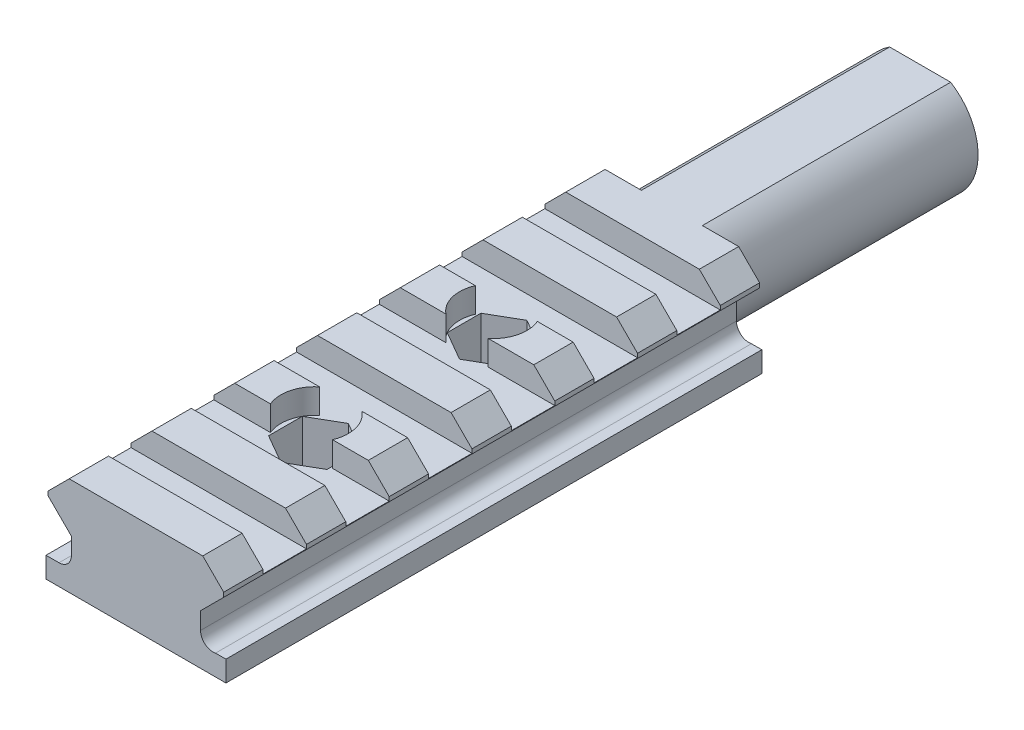
SolidWorks part; units mm, degrees
ref_plane "Front Plane" through (0, 0, 0) normal (0, 0, 1) x (1, 0, 0)
ref_plane "Top Plane" through (0, 0, 0) normal (0, 1, 0) x (1, 0, 0)
ref_plane "Right Plane" through (0, 0, 0) normal (1, 0, 0) x (0, 0, -1)
sketch "Sketch2" plane through (0, 0, 0) normal (0, 0, 1) x (1, 0, 0)
  line L0 (-9.5, -1.37) -> (9.5, -1.37)
  line L1 (-9.5, -1.37) -> (-9.5, 1.37)
  line L2 (9.5, -1.37) -> (9.5, 1.37)
  line L3 (-9.5, 1.37) -> (9.5, 1.37)
  line L4 (-9.5, -1.37) -> (9.5, 1.37) construction
  line L5 (9.5, -1.37) -> (-9.5, 1.37) construction
  line L6 (0, 0) -> (10.6, 0)
  line L7 (0, 0) -> (-10.6, 0)
  line L8 (0, 0) -> (0, -6.6)
  line L9 (0, -6.6) -> (7.8, -6.6)
  line L10 (0, -6.6) -> (-7.8, -6.6)
  line L11 (0, -1.37) -> (0, 2.8)
  line L12 (0, 2.8) -> (-18.1258, 2.8) construction
  line L13 (0, 2.8) -> (21.089, 2.8) construction
  line L14 (-8.07, 2.8) -> (8.07, 2.8)
  line L15 (-8.07, 2.8) -> (-10.87, 0)
  line L16 (-10.87, 0) -> (-7.8, -3.07)
  line L17 (-7.8, -3.07) -> (-7.8, -5.1)
  line L18 (8.07, 2.8) -> (10.87, 0)
  line L19 (7.8, -3.07) -> (10.87, 0)
  line L20 (-9.3, -6.6) -> (-10.87, -6.6)
  line L21 (7.8, -3.07) -> (7.8, -5.1331)
  line L22 (9.6133, -6.6) -> (10.87, -6.6)
  line L23 (10.87, -6.6) -> (10.87, -9.1)
  line L24 (10.87, -9.1) -> (-10.87, -9.1)
  line L25 (-10.87, -9.1) -> (-10.87, -6.6)
  line L26 (-10.6, 0) -> (-10.6, 0.27)
  line L27 (-10.6, 0) -> (-10.6, -0.27)
  line L28 (10.6, 0) -> (10.6, 0.27)
  line L29 (10.6, 0) -> (10.6, -0.27)
  arc A0 (-7.8, -5.1) -> (-9.3, -6.6) centre (-9.3, -5.1) cw
  arc A1 (7.8, -5.1331) -> (9.6133, -6.6) centre (9.3, -5.1331) ccw
  point P1 (0, 0)
  point P28 (0, 0)
  dimension "D8" = 1.5
  dimension "D9" = 1.5
  dimension "D1" = 2.74
  dimension "D2" = 19
  dimension "D3" = 10.6
  dimension "D4" = 10.6
  dimension "D5" = 15.6
  dimension "D6" = 4.17
  dimension "D7" = 9.4
  dimension "D10" = 2.5
  dimension "D11" = 21.74
  dimension "D12" = 9.6133
extrude "Boss-Extrude1" add sketch "Sketch2" along normal blind 64.75 contours A1 L21 L19 L0 L16 L17 A0 L20 L25 L24 L23 L22 | L7 L11 L3 L1 | L8 L7 L1 L0 | L6 L8 L0 L2 | L11 L6 L2 L3 | L6 L28 L18 L2 | L29 L6 L2 L19 | L7 L27 L16 L1 | L26 L7 L1 L15 | L14 L15 L3 L11 | L18 L14 L11 L3 region at (-4.75, -0.685, 0) region at (-9.927, -0.4715, 0) region at (-0.0035, -5.4607, 0) region at (4.75, -0.685, 0) region at (-9.927, 0.4715, 0) region at (-4.75, 0.685, 0) region at (9.927, -0.4715, 0) region at (4.75, 0.685, 0) region at (-4.4022, 2.0656, 0) region at (9.927, 0.4715, 0) region at (4.4022, 2.0656, 0)
sketch "Sketch3" plane through (-10.87, 0, 0) normal (-1, 0, 0) x (0, 0, 1)
  line L0 (0, -9.1) -> (0, 2.8)
  line L1 (0, 2.8) -> (4.75, 2.8)
  line L2 (64.75, 2.8) -> (0, 2.8) construction
  line L3 (14.75, 2.8) -> (14.75, -0.2)
  line L4 (4.75, 2.8) -> (10, 2.8)
  line L5 (4.75, 2.8) -> (4.75, -0.2)
  line L6 (4.75, -0.2) -> (10, -0.2)
  line L7 (10, 2.8) -> (10, -0.2)
  line L8 (14.75, 2.8) -> (20, 2.8)
  line L9 (20, 2.8) -> (20, -0.2)
  line L10 (14.75, -0.2) -> (20, -0.2)
  line L11 (24.75, 2.8) -> (24.75, -0.2)
  line L12 (24.75, 2.8) -> (30, 2.8)
  line L13 (30, 2.8) -> (30, -0.2)
  line L14 (24.75, -0.2) -> (30, -0.2)
  line L15 (34.75, 2.8) -> (34.75, -0.2)
  line L16 (34.75, 2.8) -> (40, 2.8)
  line L17 (40, 2.8) -> (40, -0.2)
  line L18 (34.75, -0.2) -> (40, -0.2)
  line L19 (44.75, 2.8) -> (44.75, -0.2)
  line L20 (44.75, 2.8) -> (50, 2.8)
  line L21 (50, 2.8) -> (50, -0.2)
  line L22 (44.75, -0.2) -> (50, -0.2)
  line L23 (54.75, 2.8) -> (54.75, -0.2)
  line L24 (54.75, 2.8) -> (60, 2.8)
  line L25 (60, 2.8) -> (60, -0.2)
  line L26 (54.75, -0.2) -> (60, -0.2)
  line L27 (0, -9.1) -> (0, -6.6) construction
  dimension "D1" = 4.75
  dimension "D2" = 3
  dimension "D3" = 5.25
  dimension "D4" = 6
  dimension "D5" = 14.75
extrude "Cut-Extrude1" cut sketch "Sketch3" against normal blind 60 contours L7 L4 L5 L6 | L3 L10 L9 L8 | L11 L14 L13 L12 | L15 L18 L17 L16 | L19 L22 L21 L20 | L23 L26 L25 L24 region at (-10.87, 1.3, 17.375) region at (-10.87, 1.3, 7.375) region at (-10.87, 1.3, 27.375) region at (-10.87, 1.3, 37.375) region at (-10.87, 1.3, 47.375) region at (-10.87, 1.3, 57.375)
sketch "Sketch4" plane through (0, 2.8, 0) normal (0, 1, 0) x (1, 0, 0)
  line L0 (0, 0) -> (0, -21.5833)
  line L1 (0, -64.75) -> (0, -43.1667)
  line L2 (0, -17.513) -> (-3.525, -19.5482)
  line L3 (-3.525, -19.5482) -> (-3.525, -23.6185)
  line L4 (-3.525, -23.6185) -> (0, -25.6537)
  line L5 (0, -25.6537) -> (3.525, -23.6185)
  line L6 (3.525, -23.6185) -> (3.525, -19.5482)
  line L7 (3.525, -19.5482) -> (0, -17.513)
  line L8 (-8.07, -64.75) -> (8.07, -64.75) construction
  line L10 (0, -47.237) -> (3.525, -45.2018)
  line L11 (3.525, -45.2018) -> (3.525, -41.1315)
  line L12 (3.525, -41.1315) -> (0, -39.0963)
  line L13 (0, -39.0963) -> (-3.525, -41.1315)
  line L14 (-3.525, -41.1315) -> (-3.525, -45.2018)
  line L15 (-3.525, -45.2018) -> (0, -47.237)
  circle A0 centre (0, -21.5833) radius 3.525 construction
  circle A1 centre (0, -43.1667) radius 3.525 construction
  circle A2 centre (0, -21.5833) radius 2.025
  circle A3 centre (0, -43.1667) radius 2.025
  circle A4 centre (0, -21.5833) radius 4.0703
  circle A5 centre (0, -43.1667) radius 4.0703
  dimension "D1" = 21.5833
  dimension "D2" = 7.05
  dimension "D3" = 7.05
extrude "Cut-Extrude2" cut sketch "Sketch4" against normal blind 9.1 contours A2 L2 L3 L4 L5 L6 L7 | A3 L10 L11 L12 L13 L14 L15 region at (1.7087, 2.8, 18.6239) region at (-1.7087, 2.8, 46.1261)
extrude "Cut-Extrude3" cut sketch "Sketch4<4>" against normal blind 59.1 contours A2 | A3 region at (1.3914, 2.8, 20.1919) region at (-1.3914, 2.8, 41.7753)
sketch "Sketch4<4>" plane through (0, 2.8, 0) normal (0, 1, 0) x (1, 0, 0) same geometry as "Sketch4"
extrude "Cut-Extrude4" cut sketch "Sketch4<5>" against normal blind 3 contours A4 | A5
sketch "Sketch4<5>" plane through (0, 2.8, 0) normal (0, 1, 0) x (1, 0, 0) same geometry as "Sketch4"
sketch "Sketch5" plane through (0, 0, 0) normal (0, 0, -1) x (-1, 0, 0)
  line L0 (0, -9.1) -> (-6, -9.1)
  line L1 (-10.87, -9.1) -> (10.87, -9.1) construction
  line L2 (0, -9.1) -> (6, -9.1)
  line L3 (6, -9.1) -> (6, 2.8)
  line L4 (8.07, 2.8) -> (-8.07, 2.8) construction
  line L5 (6, 2.8) -> (0, 2.8)
  line L6 (0, 2.8) -> (0, -9.1)
  line L7 (-6, -9.1) -> (-6, 2.8)
  line L8 (-6, 2.8) -> (0, 2.8)
  circle A0 centre (0, -3.15) radius 6
  circle A1 centre (0, -3.15) radius 7
  line M8 (-10.87, -9.1) -> (10.87, -9.1)
  line M16 (8.07, 2.8) -> (-8.07, 2.8)
extrude "Boss-Extrude2" add sketch "Sketch5" along normal blind 30 contours L8 A1 L7 A0 | L7 A1 | L7 A1 L0 A0 | L2 A1 L3 A0 | A0 L5 L6 M8 | A0 L0 L6 M16 | L3 A1 L5 A0 | L3 A1 region at (-2.5485, -3.15, 0) region at (2.5485, -3.15, 0) region at (4.456, -7.4879, 0) region at (-4.456, -7.4879, 0) region at (6.4026, -3.15, 0) region at (4.456, 1.1879, 0) region at (-6.4026, -3.15, 0) region at (-4.456, 1.1879, 0)
